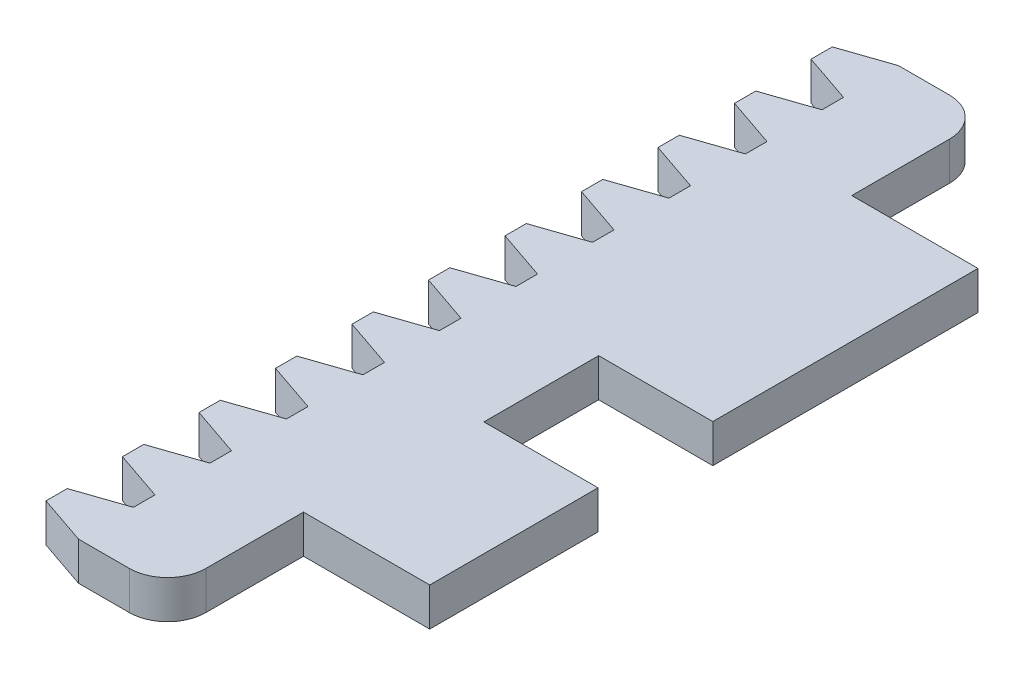
SolidWorks part; units mm, degrees
ref_plane "Front Plane" through (0, 0, 0) normal (0, 0, 1) x (1, 0, 0)
ref_plane "Top Plane" through (0, 0, 0) normal (0, 1, 0) x (1, 0, 0)
ref_plane "Right Plane" through (0, 0, 0) normal (1, 0, 0) x (0, 0, -1)
sketch "Sketch1" plane through (0, 0, 0) normal (0, 1, 0) x (1, 0, 0)
  line L4 (37.95, 21.5) -> (28.05, 21.5) construction
  line L5 (28.05, 29.157) -> (28.05, 21.5) construction
  line L6 (21.0585, 32.157) -> (25.05, 32.157) construction
  line L7 (21.0585, 32.157) -> (17.1887, 30.8335) construction
  line L8 (17.1887, 30.8335) -> (17.1887, 29.1665) construction
  line L13 (17.1887, 29.1665) -> (21.0585, 27.843) construction
  line L14 (21.0585, 26.157) -> (21.0585, 27.843) construction
  line L15 (21.0585, 26.157) -> (17.1887, 24.8335) construction
  line L16 (17.1887, 24.8335) -> (17.1887, 23.1665) construction
  line L17 (17.1887, 23.1665) -> (21.0585, 21.843) construction
  line L18 (21.0585, 20.157) -> (21.0585, 21.843) construction
  line L19 (21.0585, 20.157) -> (17.1887, 18.8335) construction
  line L20 (17.1887, 18.8335) -> (17.1887, 17.1665) construction
  line L21 (17.1887, 17.1665) -> (21.0585, 15.843) construction
  line L22 (21.0585, 14.157) -> (21.0585, 15.843) construction
  line L23 (21.0585, 14.157) -> (17.1887, 12.8335) construction
  line L24 (17.1887, 12.8335) -> (17.1887, 11.1665) construction
  line L25 (17.1887, 11.1665) -> (21.0585, 9.843) construction
  line L26 (21.0585, 8.157) -> (21.0585, 9.843) construction
  line L27 (21.0585, 8.157) -> (17.1887, 6.8335) construction
  line L28 (17.1887, 6.8335) -> (17.1887, 5.1665) construction
  line L29 (17.1887, 5.1665) -> (21.0585, 3.843) construction
  line L30 (21.0585, 2.157) -> (21.0585, 3.843) construction
  line L31 (21.0585, 2.157) -> (17.1887, 0.8335) construction
  line L32 (17.1887, 0.8335) -> (17.1887, -0.8335) construction
  line L33 (17.1887, -0.8335) -> (21.0585, -2.157) construction
  line L34 (21.0585, -3.843) -> (21.0585, -2.157) construction
  line L35 (21.0585, -3.843) -> (17.1887, -5.1665) construction
  line L36 (17.1887, -5.1665) -> (17.1887, -6.8335) construction
  line L37 (17.1887, -6.8335) -> (21.0585, -8.157) construction
  line L38 (21.0585, -9.843) -> (21.0585, -8.157) construction
  line L39 (21.0585, -9.843) -> (17.1887, -11.1665) construction
  line L40 (17.1887, -11.1665) -> (17.1887, -12.8335) construction
  line L41 (17.1887, -12.8335) -> (21.0585, -14.157) construction
  line L42 (21.0585, -15.843) -> (21.0585, -14.157) construction
  line L43 (21.0585, -15.843) -> (17.1887, -17.1665) construction
  line L44 (17.1887, -17.1665) -> (17.1887, -18.8335) construction
  line L45 (17.1887, -18.8335) -> (21.0585, -20.157) construction
  line L46 (21.0585, -21.843) -> (21.0585, -20.157) construction
  line L47 (21.0585, -21.843) -> (17.1887, -23.1665) construction
  line L48 (17.1887, -23.1665) -> (17.1887, -24.8335) construction
  line L49 (17.1887, -24.8335) -> (21.0585, -26.157) construction
  line L55 (21.0585, -27.843) -> (21.0585, -26.157) construction
  line L56 (21.0585, -27.843) -> (17.1887, -29.1665) construction
  line L57 (17.1887, -29.1665) -> (17.1887, -30.8335) construction
  line L99 (17.1887, -30.8335) -> (21.0585, -32.157) construction
  line L100 (25.05, -32.157) -> (21.0585, -32.157) construction
  line L105 (28.05, -21.5) -> (28.05, -29.157) construction
  line L107 (37.95, -21.5) -> (28.05, -21.5) construction
  line L108 (37.95, -8.3) -> (37.95, -21.5) construction
  line L109 (29, -8.3) -> (37.95, -8.3) construction
  line L110 (29, 0.7) -> (29, -8.3) construction
  line L111 (37.95, 0.7) -> (29, 0.7) construction
  line L112 (37.95, 21.5) -> (37.95, 0.7) construction
  line L113 (37.95, 21.5) -> (28.05, 21.5)
  line L114 (28.05, 29.157) -> (28.05, 21.5)
  line L115 (21.0585, 32.157) -> (25.05, 32.157)
  line L116 (21.0585, 32.157) -> (17.1887, 30.8335)
  line L117 (17.1887, 30.8335) -> (17.1887, 29.1665)
  line L118 (17.1887, 29.1665) -> (21.0585, 27.843)
  line L119 (21.0585, 26.157) -> (21.0585, 27.843)
  line L120 (21.0585, 26.157) -> (17.1887, 24.8335)
  line L121 (17.1887, 24.8335) -> (17.1887, 23.1665)
  line L122 (17.1887, 23.1665) -> (21.0585, 21.843)
  line L123 (21.0585, 20.157) -> (21.0585, 21.843)
  line L124 (21.0585, 20.157) -> (17.1887, 18.8335)
  line L125 (17.1887, 18.8335) -> (17.1887, 17.1665)
  line L126 (17.1887, 17.1665) -> (21.0585, 15.843)
  line L127 (21.0585, 14.157) -> (21.0585, 15.843)
  line L128 (21.0585, 14.157) -> (17.1887, 12.8335)
  line L129 (17.1887, 12.8335) -> (17.1887, 11.1665)
  line L130 (17.1887, 11.1665) -> (21.0585, 9.843)
  line L131 (21.0585, 8.157) -> (21.0585, 9.843)
  line L132 (21.0585, 8.157) -> (17.1887, 6.8335)
  line L133 (17.1887, 6.8335) -> (17.1887, 5.1665)
  line L134 (17.1887, 5.1665) -> (21.0585, 3.843)
  line L135 (21.0585, 2.157) -> (21.0585, 3.843)
  line L136 (21.0585, 2.157) -> (17.1887, 0.8335)
  line L137 (17.1887, 0.8335) -> (17.1887, -0.8335)
  line L138 (17.1887, -0.8335) -> (21.0585, -2.157)
  line L139 (21.0585, -3.843) -> (21.0585, -2.157)
  line L140 (21.0585, -3.843) -> (17.1887, -5.1665)
  line L141 (17.1887, -5.1665) -> (17.1887, -6.8335)
  line L142 (17.1887, -6.8335) -> (21.0585, -8.157)
  line L143 (21.0585, -9.843) -> (21.0585, -8.157)
  line L144 (21.0585, -9.843) -> (17.1887, -11.1665)
  line L145 (17.1887, -11.1665) -> (17.1887, -12.8335)
  line L146 (17.1887, -12.8335) -> (21.0585, -14.157)
  line L147 (21.0585, -15.843) -> (21.0585, -14.157)
  line L148 (21.0585, -15.843) -> (17.1887, -17.1665)
  line L149 (17.1887, -17.1665) -> (17.1887, -18.8335)
  line L150 (17.1887, -18.8335) -> (21.0585, -20.157)
  line L151 (21.0585, -21.843) -> (21.0585, -20.157)
  line L152 (21.0585, -21.843) -> (17.1887, -23.1665)
  line L153 (17.1887, -23.1665) -> (17.1887, -24.8335)
  line L154 (17.1887, -24.8335) -> (21.0585, -26.157)
  line L155 (21.0585, -27.843) -> (21.0585, -26.157)
  line L156 (21.0585, -27.843) -> (17.1887, -29.1665)
  line L157 (17.1887, -29.1665) -> (17.1887, -30.8335)
  line L160 (17.1887, -30.8335) -> (21.0585, -32.157)
  line L161 (25.05, -32.157) -> (21.0585, -32.157)
  line L162 (28.05, -21.5) -> (28.05, -29.157)
  line L163 (37.95, -21.5) -> (28.05, -21.5)
  line L164 (37.95, -8.3) -> (37.95, -21.5)
  line L165 (29, -8.3) -> (37.95, -8.3)
  line L166 (29, 0.7) -> (29, -8.3)
  line L167 (37.95, 0.7) -> (29, 0.7)
  line L168 (37.95, 21.5) -> (37.95, 0.7)
  line L169 (37.95, 28.5) -> (33.35, 28.5) construction
  line L170 (15.05, 32.157) -> (26.5, 32.157) construction
  line L171 (15.05, 32.157) -> (15.05, -32.157) construction
  line L172 (15.05, -32.157) -> (26.5, -32.157) construction
  line L173 (19.65, 32.157) -> (19.65, -32.157) construction
  line L174 (37.95, 28.5) -> (33.35, 28.5) construction
  line L175 (37.95, 28.5) -> (37.95, -28.5) construction
  line L176 (37.95, -28.5) -> (33.35, -28.5) construction
  line L177 (33.35, 28.5) -> (33.35, -28.5) construction
  line L178 (21.0585, 32.157) -> (15.05, 32.157) construction
  line L179 (15.05, -32.157) -> (21.0585, -32.157) construction
  line L180 (15.05, 32.157) -> (15.05, -32.157) construction
  line L181 (19.65, -32.157) -> (19.65, 32.157) construction
  line L182 (37.95, -28.5) -> (33.35, -28.5) construction
  line L183 (33.35, -28.5) -> (33.35, 28.5) construction
  line L184 (37.95, 28.5) -> (37.95, -28.5) construction
  line L185 (37.95, 0) -> (15.05, 0) construction
  line L186 (15.05, 0) -> (37.95, 0) construction
  line L187 (26.5, 32.157) -> (26.5, -32.157) construction
  line L188 (26.5, 32.157) -> (26.5, -32.157) construction
  line L189 (19.65, 21.5) -> (37.95, 21.5) construction
  line L190 (19.65, -21.5) -> (37.95, -21.5) construction
  line L191 (37.95, 21.5) -> (19.65, 21.5) construction
  line L192 (37.95, -2.3) -> (32, -2.3) construction
  line L193 (32, -2.3) -> (32, -5.3) construction
  line L194 (32, -5.3) -> (37.95, -5.3) construction
  line L195 (29, -3.8) -> (37.95, -3.8) construction
  line L196 (34.95, 0.7) -> (34.95, 18.5) construction
  line L197 (34.95, -8.3) -> (34.95, -18.5) construction
  line L198 (34.95, 18.5) -> (19.65, 18.5) construction
  line L199 (19.65, -18.5) -> (34.95, -18.5) construction
  line L200 (34.95, 18.5) -> (34.95, 21.5) construction
  line L201 (34.95, 18.5) -> (37.95, 18.5) construction
  line L202 (34.95, -18.5) -> (37.95, -18.5) construction
  line L203 (34.95, -18.5) -> (34.95, -21.5) construction
  line L204 (37.15, 28.5) -> (37.15, -28.5) construction
  line L205 (34.15, 28.5) -> (34.15, -28.5) construction
  line L206 (18.85, 32.157) -> (18.85, -32.157) construction
  line L207 (15.85, 32.157) -> (15.85, -32.157) construction
  line L208 (37.15, 28.5) -> (37.15, 0.7) construction
  line L209 (34.15, 28.5) -> (34.15, 0.7) construction
  line L210 (18.85, 32.157) -> (18.85, -32.157) construction
  line L211 (15.85, 32.157) -> (15.85, -32.157) construction
  line L212 (37.15, -8.3) -> (37.15, -28.5) construction
  line L213 (34.15, -8.3) -> (34.15, -28.5) construction
  arc A2 (28.05, 29.157) -> (25.05, 32.157) centre (25.05, 29.157) ccw construction
  arc A3 (25.05, -32.157) -> (28.05, -29.157) centre (25.05, -29.157) ccw construction
  arc A4 (28.05, 29.157) -> (25.05, 32.157) centre (25.05, 29.157) ccw
  arc A5 (25.05, -32.157) -> (28.05, -29.157) centre (25.05, -29.157) ccw
sketch "Sketch2" plane through (0, 0, 0) normal (0, 0, 1) x (1, 0, 0)
  line L1 (37.95, -3) -> (15.05, -3)
  line L2 (37.95, -3) -> (37.95, 0)
  line L3 (37.95, 0) -> (15.05, 0)
  line L4 (15.05, -3) -> (15.05, 0)
  line L5 (21, -3) -> (-21, -3) construction
extrude "Boss-Extrude1" add sketch "Sketch1" against normal up to vertex (3 mm away) up to point (15.05, -3, 0)
ref_plane "gear" through (0, 0, 2.3) normal (0, 0, 1) x (1, 0, 0)
ref_plane "front" through (0, 0, 21.5) normal (0, 0, 1) x (1, 0, 0)
ref_plane "back" through (0, 0, -21.5) normal (0, 0, 1) x (1, 0, 0)
ref_plane "top" through (37.15, 0, 0) normal (1, 0, 0) x (0, 0, -1)
ref_plane "bottom" through (15.85, 0, 0) normal (1, 0, 0) x (0, 0, -1)
ref_plane "sym" through (26.5, 0, 0) normal (1, 0, 0) x (0, 0, -1)
